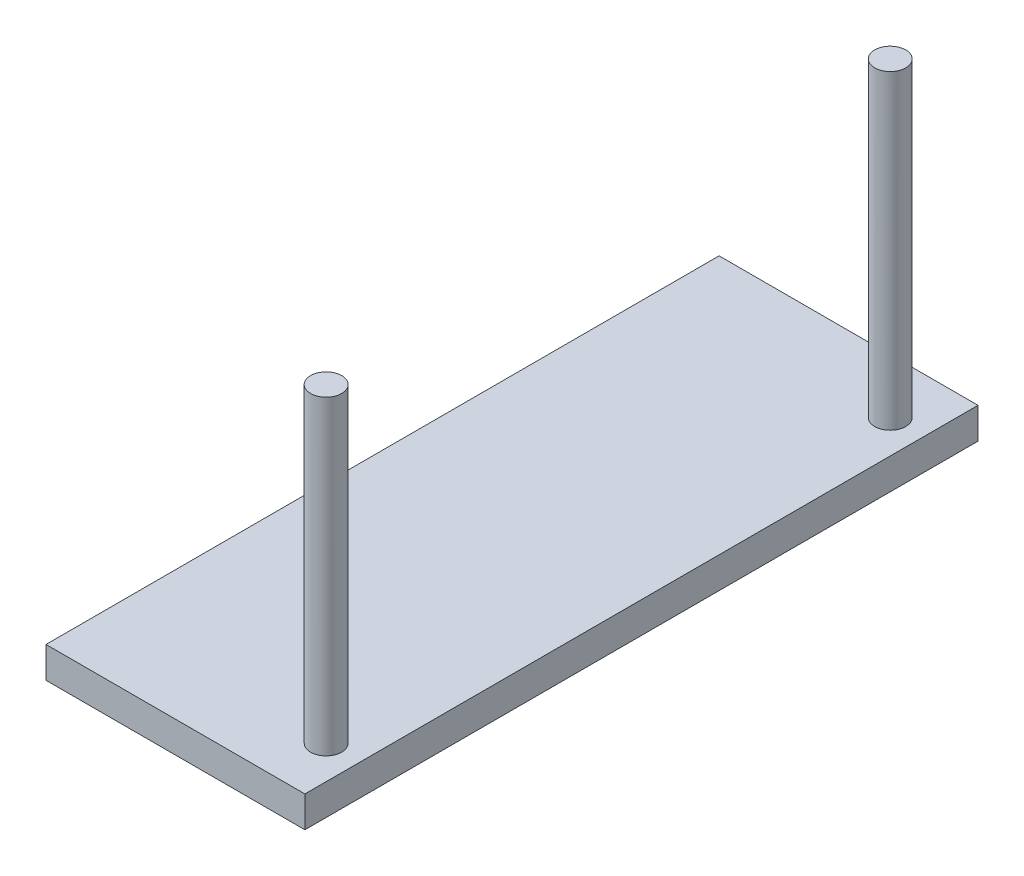
SolidWorks part; units mm, degrees
ref_plane "Front Plane" through (0, 0, 0) normal (0, 0, 1) x (1, 0, 0)
ref_plane "Top Plane" through (0, 0, 0) normal (0, 1, 0) x (1, 0, 0)
ref_plane "Right Plane" through (0, 0, 0) normal (1, 0, 0) x (0, 0, -1)
sketch "Sketch1" plane through (0, 0, 0) normal (0, 1, 0) x (1, 0, 0)
  line L1 (-12.5, -32.5) -> (12.5, -32.5)
  line L2 (-12.5, -32.5) -> (-12.5, 32.5)
  line L3 (-12.5, 32.5) -> (12.5, 32.5)
  line L4 (12.5, -32.5) -> (12.5, 32.5)
  line L5 (-12.5, -32.5) -> (12.5, 32.5) construction
  line L6 (-12.5, 32.5) -> (12.5, -32.5) construction
  point P0 (0, 0)
  dimension "D1" = 65
  dimension "D2" = 25
extrude "Boss-Extrude1" add sketch "Sketch1" along normal blind 3
sketch "Sketch2" plane through (0, 3, 0) normal (0, 1, 0) x (1, 0, 0)
  line L0 (-70.6517, 0) -> (70.6517, 0) construction
  line L1 (12.5, -32.5) -> (12.5, 32.5) construction
  circle A0 centre (9.2897, 27.2349) radius 1.5
  circle A1 centre (9.2897, -27.2349) radius 1.5
  point P8 (0, 0)
  dimension "D1" = 3
  dimension "D2" = 3.2103
  dimension "D3" = 54.4698
extrude "Boss-Extrude2" add sketch "Sketch2" along normal blind 30
